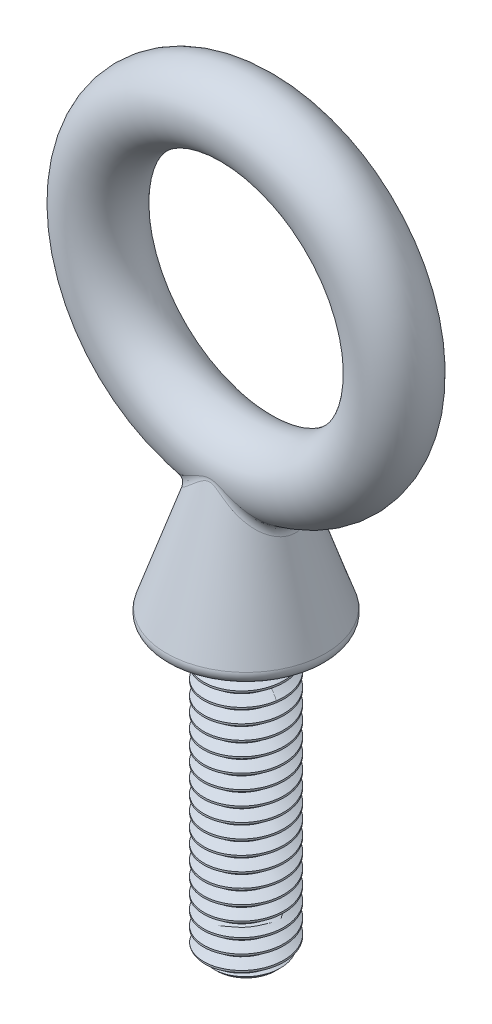
SolidWorks part; units mm, degrees
ref_plane "Front Plane" through (0, 0, 0) normal (0, 0, 1) x (1, 0, 0)
ref_plane "Top Plane" through (0, 0, 0) normal (0, 1, 0) x (1, 0, 0)
ref_plane "Right Plane" through (0, 0, 0) normal (1, 0, 0) x (0, 0, -1)
sketch "Sketch1" plane through (0, 0, 0) normal (0, 0, 1) x (1, 0, 0)
  line L0 (0, -18.2562) -> (0, -57.15) construction
  line L1 (-3.9687, -57.15) -> (3.9688, -57.15) construction
  line L3 (0, -18.2562) -> (0, -11.1125) construction
  line L4 (-7.9375, -28.575) -> (7.9375, -28.575) construction
  circle A0 centre (0, 0) radius 18.2562 construction
  circle A1 centre (0, 14.6844) radius 3.5719 construction
  circle A2 centre (0, 0) radius 11.1125 construction
  point P7 (0, -18.2562)
  point P9 (0, -28.575)
  point P10 (0, 18.2562)
  point P11 (0, 11.1125)
  point P14 (0, -57.15)
  point P19 (0, -14.6844)
  point P21 (0, -28.575)
  dimension "A" = 7.1437
  dimension "Eye Dia." = 22.225
  dimension "Overall Lg." = 75.4062
  dimension "Shank Lg." = 28.575
  dimension "OD" = 36.5125
  dimension "Thread Lg." = 28.575
  dimension "Thread OD" = 7.9375
  dimension "Shoulder Dia." = 15.875
  dimension "Thickness" = 10.3187
sketch "Sketch2" plane through (0, 0, 0) normal (0, 1, 0) x (1, 0, 0)
  circle A0 centre (0, 0) radius 3.9688
extrude "Boss-Extrude1" add sketch "Sketch2" against normal up to vertex (57.15 mm away) from vertex at -28.575 starting at point (0, -28.575, 0)
sketch "Sketch3" plane through (0, -57.15, 0) normal (0, -1, 0) x (1, 0, 0)
  circle A1 centre (0, 0) radius 3.9688
  circle A2 centre (0, 0) radius 3.9688
  point P0 (3.9688, 0)
  point P1 (0, -3.9688)
  dimension "D1" = 0
curve "Helix/Spiral1" pitch 1.4111 height 29.9861 turns 21.25 parameters "Pitch"=1.4111
sketch "Sketch4" plane through (0, 0, 0) normal (0, 0, 1) x (1, 0, 0)
  line L0 (4.1215, -57.0618) -> (4.1215, -58.4729) construction
  line L1 (4.1215, -58.4729) -> (2.8994, -57.7674) construction
  line L2 (2.8994, -57.7674) -> (4.1215, -57.0618) construction
  line L3 (3.0522, -57.6792) -> (3.0522, -57.8556) construction
  line L4 (3.9688, -57.15) -> (3.9688, -58.3847) construction
  line L5 (2.8994, -57.7674) -> (3.0522, -57.7674) construction
  line L6 (3.9688, -57.7674) -> (4.1215, -57.7674) construction
  line L7 (4.0451, -57.1059) -> (3.0522, -57.6792)
  line L8 (3.0522, -57.6792) -> (3.0522, -57.8556)
  line L9 (3.0522, -57.8556) -> (4.0451, -58.4288)
  line L10 (4.0451, -58.4288) -> (4.0451, -57.1059)
  point P13 (4.0451, -57.7674)
  dimension "D1" = 1.4111
  dimension "D2" = 0.1764
sweep "Cut-Sweep1" cut profiles "Sketch4" path "Helix/Spiral1" align with end faces yes
sketch "Sketch5" plane through (0, -57.15, 0) normal (0, -1, 0) x (1, 0, 0)
  circle A0 centre (0, 0) radius 2.8994
extrude "Cut-Extrude1" cut sketch "Sketch5" against normal through all draft 45 flip side to cut
sketch "Sketch6" plane through (0, 0, 0) normal (1, 0, 0) x (0, 0, -1)
  circle A0 centre (0, 14.6844) radius 3.5719
ref_axis "Axis1" through (0, 0, -7.6398) along (0, 0, 1)
revolve "Revolve1" add sketch "Sketch6" angle 360 about axis through (0, 0, -7.6398) along (0, 0, 1)
sketch "Sketch7" plane through (0, -28.575, 0) normal (0, 1, 0) x (1, 0, 0)
  circle A1 centre (0, 0) radius 3.9688
  circle A2 centre (0, 0) radius 3.9688
  dimension "D1" = 0
extrude "Boss-Extrude2" [suppressed] add sketch "Sketch7" along normal up to vertex (9.525 mm away)
sketch "Sketch8" plane through (0, 0, 0) normal (0, 0, 1) x (1, 0, 0)
  line L0 (0, -28.575) -> (0, -14.6844)
  line L1 (0, -14.6844) -> (-3.5719, -14.6844)
  line L2 (-7.0445, -28.575) -> (-7.9375, -28.575) construction
  line L3 (-7.9375, -28.575) -> (-7.9375, -27.682) construction
  line L5 (-7.9375, -28.575) -> (7.9375, -28.575) construction
  line L6 (-7.89, -27.3948) -> (-3.5719, -14.6844)
  line L9 (-7.0445, -28.575) -> (0, -28.575)
  arc A0 (-7.89, -27.3948) -> (-7.0445, -28.575) centre (-7.0445, -27.682) ccw
  circle A1 centre (0, -14.6844) radius 3.5719 construction
  dimension "D1" = 0.893
revolve "Revolve2" add sketch "Sketch8" angle 360 about L0
fillet "Fillet1" radius 0.893 1 edges at (3.9917, -17.2295, 1.9363)
sketch "SketchX" plane through (0, 0, 0) normal (1, 0, 0) x (0, 0, -1)
  line L0 (3.9688, -57.15) -> (3.9688, -31.3972) construction
  dimension "D1" = 25.7528
equation "\"D3@Helix/Spiral1\" = \"Pitch@Helix/Spiral1\" + \"Thread Lg.@Sketch1\""
equation "\"D1@Sketch4\" = \"Pitch@Helix/Spiral1\""
equation "\"D2@Sketch4\" = \"D1@Sketch4\" / 8"
equation "\"D1@Sketch8\" = \"A@Sketch1\" / 8"
equation "\"D1@Fillet1\" = \"A@Sketch1\" / 8"
equation "\"D1@SketchX\" = 1 + \"Pitch@Helix/Spiral1\" /  4"
